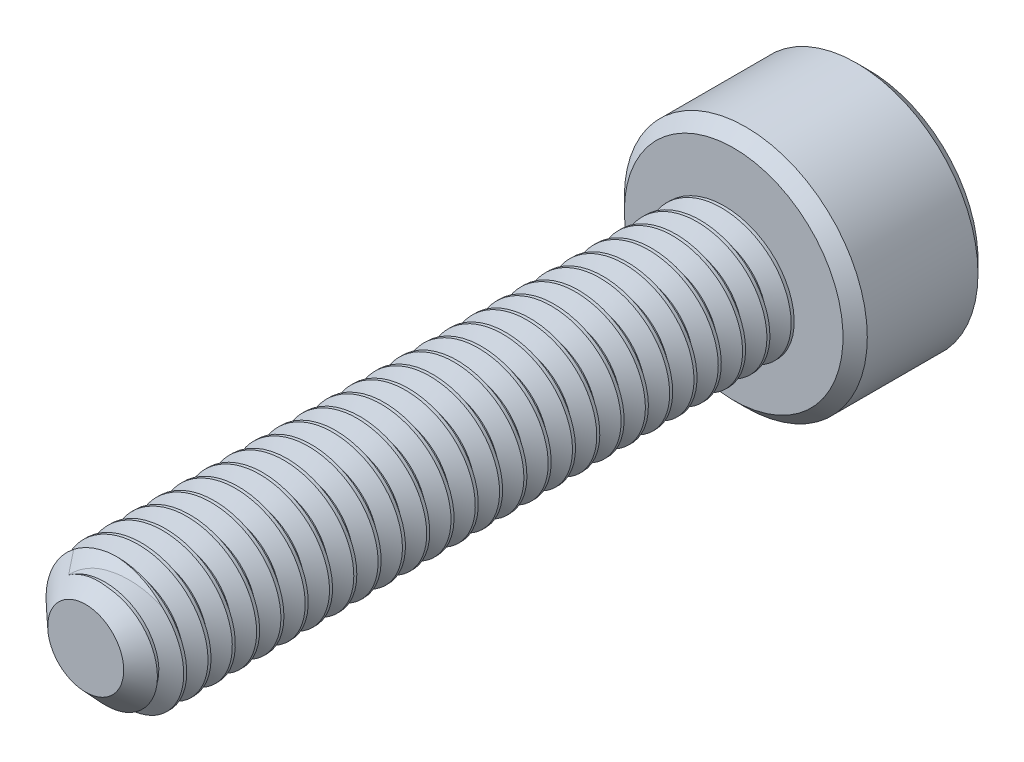
SolidWorks part; units mm, degrees
material "AISI 304"
ref_plane "Front Plane" through (0, 0, 0) normal (0, 0, 1) x (1, 0, 0)
ref_plane "Top Plane" through (0, 0, 0) normal (0, 1, 0) x (1, 0, 0)
ref_plane "Right Plane" through (0, 0, 0) normal (1, 0, 0) x (0, 0, -1)
sketch "Sketch1" plane through (0, 0, 0) normal (0, 0, 1) x (1, 0, 0)
  circle A0 centre (0, 0) radius 1.25
  dimension "OD" = 2.5
extrude "Extrude1" add sketch "Sketch1" against normal blind 12
sketch "Sketch2" plane through (0, 0, 0) normal (0, 0, 1) x (1, 0, 0)
  circle A0 centre (0, 0) radius 1.25 construction
  circle A1 centre (0, 0) radius 1.25
curve "Helix/Spiral1" pitch 0.45 height 12.45 turns 27.6667 parameters "pitch"=0.45
sketch "Sketch3" plane through (0, 0, 0) normal (1, 0, 0) x (0, 0, -1)
  line L0 (-0.3938, 1.25) -> (-0.225, 0.9577)
  line L1 (-0.225, 0.9577) -> (-0.1687, 0.9577)
  line L2 (-0.1687, 0.9577) -> (0, 1.25)
  line L3 (-0.3938, 1.25) -> (0, 1.25)
  line L4 (-0.1969, 1.25) -> (-0.1969, 0.9577) construction
  line L5 (-0.3094, 1.1039) -> (-0.0844, 1.1039) construction
  line L6 (0, 1.25) -> (0, -1.25) construction
  dimension "D1" = 0.0563
  dimension "D2" = 0.225
  dimension "D3" = 60
sweep "Cut-Sweep1" cut profiles "Sketch3" path "Helix/Spiral1"
sketch "Sketch4" plane through (0, 0, 0) normal (1, 0, 0) x (0, 0, -1)
  line L0 (0.5094, 1.25) -> (0, 0.7037)
  line L1 (0, 0.7037) -> (0, 1.25)
  line L2 (0.5094, 1.25) -> (0, 1.25)
  line L3 (-0.3938, 1.25) -> (0, 1.25) construction
  line L4 (0, 0) -> (7.0209, 0) construction
  dimension "D1" = 47
  dimension "D2" = 0.254
revolve "Cut-Revolve1" cut sketch "Sketch4" angle 360 about L4
sketch "Sketch5" plane through (0, 0, 0) normal (1, 0, 0) x (0, 0, -1)
  line L0 (12, -1.2229) -> (12, 0.4789) construction
  line L1 (12, 1.377) -> (28.1202, 1.377)
  line L2 (12, 1.377) -> (12, 0)
  line L3 (12, 0) -> (28, 0)
  line L4 (28, 1.0468) -> (28, 0)
  line L5 (28.1202, 1.377) -> (28, 1.0468)
  line L6 (0, 0) -> (9.9695, 0) construction
  point P3 (28, 1.377)
  point P10 (28, 1.377)
  dimension "D1" = 0.3302
  dimension "Thread min" = 28
  dimension "D2" = 0.127
  dimension "D3" = 20
revolve "partially thread" [suppressed] add sketch "Sketch5" angle 360 about L6
sketch "Sketch6" plane through (0, 0, -12) normal (0, 0, -1) x (-1, 0, 0)
  circle A0 centre (0, 0) radius 2.25
  dimension "head dia" = 4.5
extrude "Extrude2" add sketch "Sketch6" along normal blind 2.5
sketch "Sketch7" plane through (0, 0, -14.5) normal (0, 0, -1) x (-1, 0, 0)
  line L1 (0, 1.1547) -> (-1, 0.5774)
  line L2 (-1, 0.5774) -> (-1, -0.5774)
  line L3 (-1, -0.5774) -> (0, -1.1547)
  line L4 (0, -1.1547) -> (1, -0.5774)
  line L5 (1, -0.5774) -> (1, 0.5774)
  line L6 (1, 0.5774) -> (0, 1.1547)
  circle A0 centre (0, 0) radius 1 construction
  dimension "hex dia" = 2
extrude "Cut-Extrude1" cut sketch "Sketch7" against normal blind 1.5
sketch "Sketch8" plane through (0, 0, -14.5) normal (0, 0, -1) x (-1, 0, 0)
  circle A0 centre (0, 0) radius 1.1547
extrude "Cut-Extrude2" cut sketch "Sketch8" against normal through all draft 45
chamfer "Chamfer1" distance 0.225 angle 45 2 edges at (-2.25, 0, -14.5) (-2.25, 0, -12)
sketch "Sketch9" plane through (0, 0, 0) normal (1, 0, 0) x (0, 0, -1)
  line L0 (0, 1.25) -> (0, -1.25) construction
  line L1 (2.475, 1.25) -> (2.475, -1.25) construction
  dimension "D1" = 2.475
equation "\"D3@Helix/Spiral1\" = \"screw length@Extrude1\"+\"pitch@Helix/Spiral1\""
equation "\"D1@Sketch3\" = \"pitch@Helix/Spiral1\"*.125"
equation "\"D2@Sketch3\" = \"pitch@Helix/Spiral1\"*.5"
equation "\"D1@Cut-Extrude1\" = \"hex dia@Sketch7\"*.75"
equation "\"D1@Chamfer1\" = \"head dia@Sketch6\"*.05"
equation "\"D1@Sketch9\" = \"pitch@Helix/Spiral1\"*5.5"
